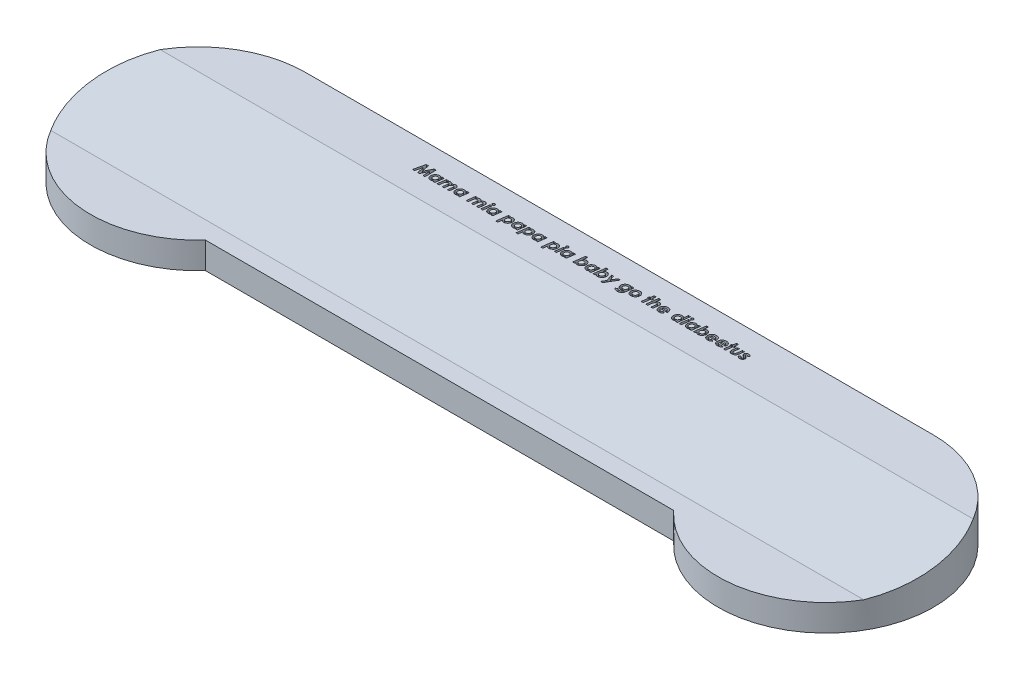
SolidWorks part; units mm, degrees
ref_plane "Front Plane" through (0, 0, 0) normal (0, 0, 1) x (1, 0, 0)
ref_plane "Top Plane" through (0, 0, 0) normal (0, 1, 0) x (1, 0, 0)
ref_plane "Right Plane" through (0, 0, 0) normal (1, 0, 0) x (0, 0, -1)
sketch "Sketch1" plane through (0, 0, 0) normal (0, 1, 0) x (1, 0, 0)
  line L1 (72, -30.5) -> (-72, -30.5) construction
  line L3 (136.3, 30.5) -> (-41.5, 30.5)
  line L5 (72, -30.5) -> (-72, 30.5) construction
  line L6 (72, 30.5) -> (-11.3836, -4.8222) construction
  line L7 (-18.9168, -20.5) -> (113.7168, -20.5)
  line L8 (-58.9884, -24.9881) -> (-72, -30.5) construction
  line L9 (-41.5, 0) -> (-72, 0) construction
  line L10 (136.3, 0) -> (166.8, 0) construction
  arc A0 (-41.5, 30.5) -> (-18.9168, -20.5) centre (-41.5, 0) ccw
  arc A1 (113.7168, -20.5) -> (136.3, 30.5) centre (136.3, 0) ccw
  point P0 (0, 0)
  dimension "D4" = 61
  dimension "D2" = 177.8
  dimension "D1" = 144
  dimension "D3" = 61
  dimension "D6" = 10
extrude "Boss-Extrude1" add sketch "Sketch1" along normal blind 15
sketch "Sketch3" plane through (0, 0, 0) normal (1, 0, 0) x (0, 0, -1)
  line L0 (-30.5, 7.5) -> (-15.5, 7.5)
  line L1 (-30.5, 15) -> (-30.5, 0) construction
  line L2 (30.5, 11.8179) -> (15.5, 11.8179)
  line L3 (30.5, 15) -> (30.5, 0) construction
  line L4 (15.5, 11.8179) -> (-15.5, 7.5)
  line L5 (-30.5, 7.5) -> (-30.5, 24.9443)
  line L6 (-30.5, 24.9443) -> (30.5, 24.9443)
  line L7 (30.5, 24.9443) -> (30.5, 11.8179)
  dimension "D1" = 15
  dimension "D2" = 15
extrude "Cut-Extrude2" cut sketch "Sketch3" along normal through all both and the other way through all
sketch "Sketch2" plane through (0, 0, 0) normal (0, 1, 0) x (1, 0, 0)
  line L6 (136.3, 25.5) -> (-41.5, 25.5)
  line L7 (-21.2515, -15.5) -> (116.0515, -15.5)
  line L8 (136.3, 25.5) -> (-41.5, 25.5)
  line L9 (-21.2515, -15.5) -> (116.0515, -15.5)
  arc A8 (116.0515, -15.5) -> (136.3, 25.5) centre (136.3, 0) ccw
  arc A9 (-41.5, 25.5) -> (-21.2515, -15.5) centre (-41.5, 0) ccw
  arc A10 (116.0515, -15.5) -> (136.3, 25.5) centre (136.3, 0) ccw
  arc A11 (-41.5, 25.5) -> (-21.2515, -15.5) centre (-41.5, 0) ccw
  dimension "D1" = 5
extrude "Cut-Extrude3" cut sketch "Sketch2" along normal blind 5
sketch "Sketch4" plane through (0, 0, 0) normal (1, 0, 0) x (0, 0, -1)
  line L0 (25.5, 5) -> (25.5, 9.3179)
  line L1 (25.5, 9.3179) -> (15.5, 9.3179)
  line L2 (15.5, 9.3179) -> (-15.5, 5)
  line L3 (-15.5, 5) -> (25.5, 5)
  line L4 (30.5, 11.8179) -> (15.5, 11.8179) construction
  line L5 (-15.5, 7.5) -> (-30.5, 7.5) construction
  line L6 (15.5, 11.8179) -> (-15.5, 7.5) construction
  dimension "D1" = 2.5
  dimension "D2" = 2.5
  dimension "D3" = 2.4761
extrude "Cut-Extrude4" cut sketch "Sketch4" along normal blind 116.102 and the other way blind 21
fillet "Fillet1" radius 6.35 1 edges at (47.551, 9.3179, -15.5)
sketch "Sketch5" plane through (0, 0, -30.5) normal (0, 0, -1) x (-1, 0, 0)
  line L1 (33.55, 0) -> (-33.55, 0) construction
  line L5 (-136.3, 11.8179) -> (-136.3, 0) construction
  line L6 (41.5, 11.8179) -> (41.5, 0) construction
  circle A3 centre (-85.5, 0) radius 5.08
  circle A4 centre (-47.4, 0) radius 5.08
  circle A5 centre (-9.3, 0) radius 5.08
  point P10 (-136.3, 5.9089)
  dimension "D1" = 50.8
  dimension "D2" = 50.8
  dimension "D3" = 38.1
  dimension "D4" = 38.1
extrude "Cut-Extrude5" cut sketch "Sketch5" against normal blind 7.62
sketch "Sketch6" plane through (0, 11.8179, 0) normal (0, 1, 0) x (1, 0, 0)
  text T0 "<b><i>Mama mia papa pia baby go the diabeetus</i></b>"
extrude "Cut-Extrude6" cut sketch "Sketch6" against normal blind 1.27
